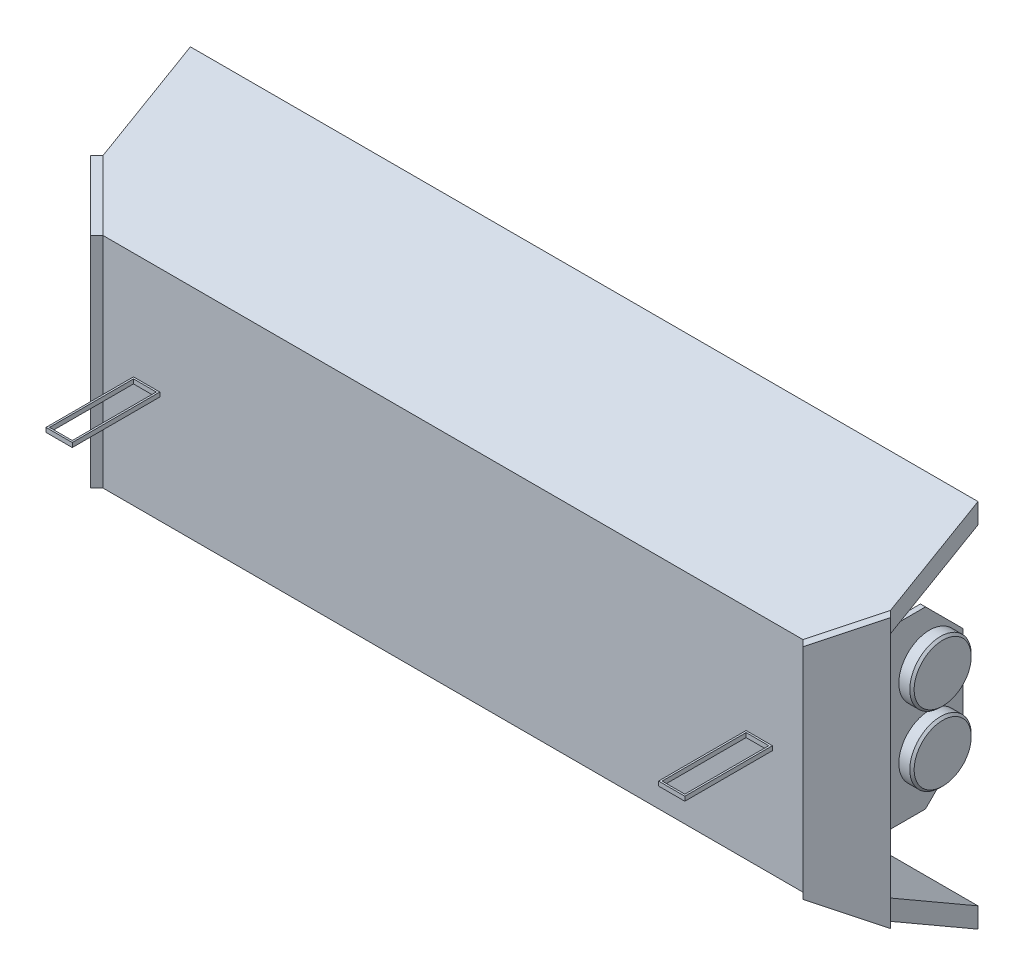
SolidWorks part; units mm, degrees
ref_plane "Top Plane" through (0, 0, 0) normal (0, 0, 1) x (1, 0, 0)
ref_plane "Front Plane" through (0, 0, 0) normal (0, 1, 0) x (1, 0, 0)
ref_plane "Right Plane" through (0, 0, 0) normal (1, 0, 0) x (0, 0, -1)
sketch "Sketch1" plane through (0, 0, 0) normal (1, 0, 0) x (0, 0, -1)
  line L0 (-0.15, -0.125) -> (-0.15, 0.125)
  line L1 (-0.15, -0.125) -> (0, -0.2116)
  line L2 (0, 55) -> (0, -55) construction
  line L3 (0, -0.2116) -> (0, -0.1885)
  line L4 (0, -0.1885) -> (-0.13, -0.1135)
  line L5 (-0.13, -0.1135) -> (-0.13, 0.1135)
  line L6 (-0.13, 0.1135) -> (0, 0.1885)
  line L7 (0, 0.1885) -> (0, 0.2116)
  line L8 (0, 0.2116) -> (-0.15, 0.125)
  line L9 (-0.13, 0) -> (0, 0) construction
  point P5 (-0.13, -0.1121)
  dimension "D1" = 0.25
  dimension "D2" = 0.15
  dimension "D3" = 0.02
  dimension "D4" = 0.02
  dimension "D5" = 60
extrude "Boss-Extrude1" add sketch "Sketch1" along normal mid plane 0.9
chamfer "Chamfer1" distance 0.05 angle 45 2 edges at (-0.45, 0, 0.15) (0.45, 0, 0.15)
sketch "Sketch2" plane through (0.275, 0, 0.275) normal (0.7071, 0, 0.7071) x (0.7071, 0, -0.7071)
  line L0 (0.1768, 0.125) -> (0.2475, 0.1539)
  line L1 (0.2475, 0.1539) -> (0.2475, -0.1539)
  line L2 (0.2475, -0.1539) -> (0.1768, -0.125)
  line L3 (0.1768, -0.125) -> (0.1768, 0.125)
extrude "Boss-Extrude2" add sketch "Sketch2" along normal blind 0.01
mirror "Mirror1" about plane through (0, 0, 0) normal (1, 0, 0) of "Boss-Extrude2"
sketch "Sketch3" plane through (0, 0, 0.13) normal (0, 0, -1) x (-1, 0, 0)
  line L0 (-0.4126, 0) -> (-0.45, 0) construction
  line L1 (-0.4126, 0.1) -> (-0.4069, 0.1)
  line L2 (-0.4126, 0.1) -> (-0.4126, -0.1)
  line L3 (-0.4126, -0.1) -> (-0.4069, -0.1)
  line L4 (-0.4069, 0.1) -> (-0.4069, -0.1)
  line L5 (-0.45, -0.1308) -> (-0.45, 0.1308) construction
extrude "Boss-Extrude3" add sketch "Sketch3" along normal blind 0.15
sketch "Sketch4" plane through (0, 0, 0.13) normal (0, 0, -1) x (-1, 0, 0)
  line L0 (-0.4126, -0.1) -> (-0.4069, -0.1) construction
  line L1 (-0.4069, 0.1) -> (-0.3906, 0.1)
  line L2 (-0.4069, 0.1) -> (-0.4069, -0.1)
  line L3 (-0.4069, -0.1) -> (-0.3906, -0.1)
  line L4 (-0.3906, 0.1) -> (-0.3906, -0.1)
extrude "Boss-Extrude4" add sketch "Sketch4" along normal blind 0.005
sketch "Sketch5" plane through (0, 0, 0) normal (0, 1, 0) x (1, 0, 0)
  line L0 (0.4, -0.15) -> (-0.4, -0.15) construction
  line L1 (0.335, -0.15) -> (0.365, -0.15)
  line L2 (0.335, -0.15) -> (0.335, -0.25)
  line L3 (0.335, -0.25) -> (0.365, -0.25)
  line L4 (0.365, -0.15) -> (0.365, -0.25)
  line L5 (-0.365, -0.2) -> (-0.337, -0.2) construction
  line L6 (0.363, -0.152) -> (0.337, -0.152)
  line L7 (0.363, -0.152) -> (0.363, -0.248)
  line L8 (0.363, -0.248) -> (0.337, -0.248)
  line L9 (0.337, -0.152) -> (0.337, -0.248)
  line L10 (-0.365, -0.15) -> (-0.335, -0.15)
  line L11 (-0.365, -0.15) -> (-0.365, -0.25)
  line L12 (-0.365, -0.25) -> (-0.335, -0.25)
  line L13 (-0.335, -0.15) -> (-0.335, -0.25)
  line L14 (-0.363, -0.152) -> (-0.337, -0.152)
  line L15 (-0.363, -0.152) -> (-0.363, -0.248)
  line L16 (-0.363, -0.248) -> (-0.337, -0.248)
  line L17 (-0.337, -0.152) -> (-0.337, -0.248)
  line L18 (-0.35, -0.15) -> (-0.35, -0.248) construction
  line L19 (-0.45, 0) -> (-0.45, -0.1) construction
  line L20 (0.35, -0.15) -> (0.35, -0.248) construction
  line L21 (0.365, -0.2) -> (0.363, -0.2) construction
  line L22 (0.45, 0) -> (0.45, -0.1) construction
  dimension "D1" = 0.03
  dimension "D2" = 0.002
  dimension "D3" = 0.002
  dimension "D4" = 0.1
  dimension "D5" = 0.1
  dimension "D6" = 0.1
extrude "Boss-Extrude5" add sketch "Sketch5" along normal mid plane 0.005
mirror "Mirror2" about plane through (0, 0, 0) normal (1, 0, 0) of "Boss-Extrude4", "Boss-Extrude3"
sketch "Sketch6" plane through (0.4069, 0, 0) normal (-1, 0, 0) x (0, 0, 1)
  line L0 (0.018, 0.0396) -> (0.018, -0.0396) construction
  line L1 (0.018, 0) -> (-0.02, 0) construction
  line L2 (-0.02, 0.1) -> (-0.02, -0.1) construction
  circle A0 centre (0.018, 0.0396) radius 0.025
  circle A1 centre (0.018, -0.0396) radius 0.025
  point P8 (0.018, 0)
  dimension "D1" = 0.05
extrude "Boss-Extrude6" add sketch "Sketch6" along normal up to next
sketch "Sketch7" plane through (-0.4126, 0, 0) normal (-1, 0, 0) x (0, 0, 1)
  line L0 (-0.02, 0.1) -> (0.0226, 0.1)
  line L1 (-0.02, 0.1) -> (0.13, 0.1) construction
  line L2 (0.0226, 0.1) -> (-0.02, 0.0574)
  line L3 (-0.02, 0.1) -> (-0.02, -0.1) construction
  line L4 (-0.02, 0.0574) -> (-0.02, 0.1)
  line L5 (-0.02, -0.1) -> (0.0226, -0.1)
  line L6 (-0.02, -0.1) -> (0.13, -0.1) construction
  line L7 (0.0226, -0.1) -> (-0.02, -0.0574)
  line L8 (-0.02, -0.0574) -> (-0.02, -0.1)
  point P13 (-0.02, -0.0587)
  point P15 (0.0191, -0.1)
  point P16 (-0.02, 0.055)
  dimension "D1" = 45
extrude "Cut-Extrude1" cut sketch "Sketch7" against normal through all
sketch "Sketch8" plane through (0.4126, 0, 0) normal (1, 0, 0) x (0, 0, -1)
  circle A0 centre (-0.018, 0.0396) radius 0.0351
  circle A1 centre (-0.018, -0.0396) radius 0.0351
extrude "Boss-Extrude7" add sketch "Sketch8" along normal blind 0.015
chamfer "Chamfer2" distance 0.0025 angle 45 2 edges at (0.4276, 0.0396, -0.0171) (0.4276, -0.0396, -0.0171)
mirror "Mirror3" about plane through (0, 0, 0) normal (1, 0, 0) of "Chamfer2", "Boss-Extrude7"
